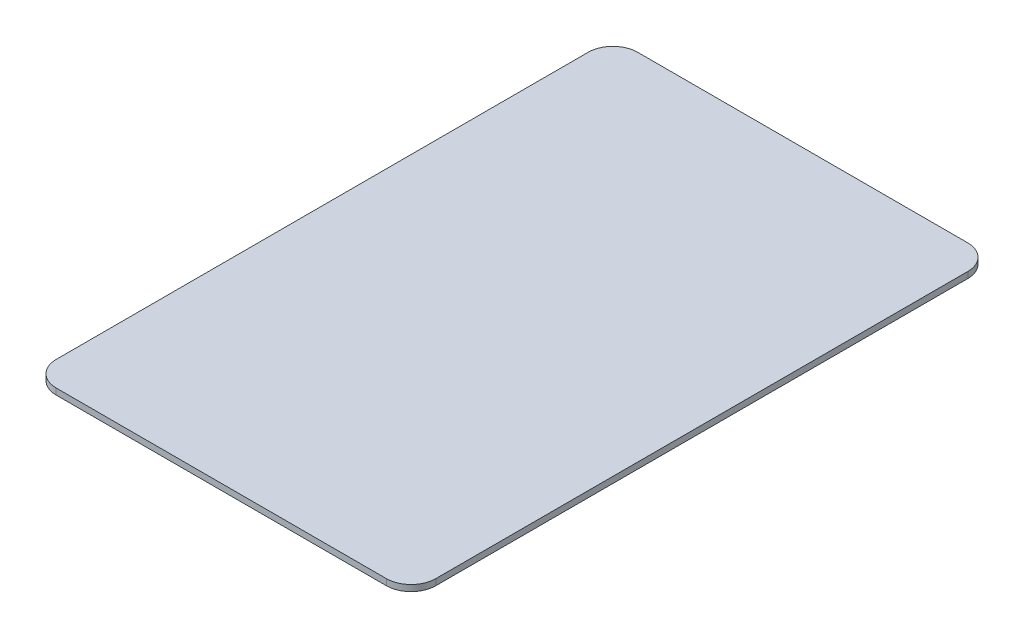
SolidWorks part; units mm, degrees
ref_plane "Front Plane" through (0, 0, 0) normal (0, 0, 1) x (1, 0, 0)
ref_plane "Top Plane" through (0, 0, 0) normal (0, 1, 0) x (1, 0, 0)
ref_plane "Right Plane" through (0, 0, 0) normal (1, 0, 0) x (0, 0, -1)
sketch "Sketch1" plane through (0, 0, 0) normal (0, 1, 0) x (1, 0, 0)
  line L1 (0, 0) -> (97.4242, 0)
  line L2 (0, 0) -> (0, 149.225)
  line L3 (0, 149.225) -> (97.4242, 149.225)
  line L4 (97.4242, 0) -> (97.4242, 149.225)
  dimension "D1" = 97.4242
  dimension "D2" = 149.225
base flange "Base-Flange1" sketch "Sketch1" thickness 1.5875 reverse thickness direction no parameters "D1"=1
fillet "Fillet1" radius 6.35 4 edges at (0, -0.7937, -149.225) (97.4242, -0.7937, -149.225) (0, -0.7937, 0) (97.4242, -0.7937, 0)
sketch "Bend-Lines1" [suppressed] plane through (0, 0, 0) normal (0, 1, 0) x (1, 0, 0)
sketch "Bounding-Box1" [suppressed] plane through (0, 0, 0) normal (0, 1, 0) x (1, 0, 0)
sheet metal parameters "Sheet-Metal1" thickness 1.5875 parameters "D1"=1
flat pattern "Flat-Pattern1" [suppressed]
sketch "Bend-Lines2" plane through (0, 0, 0) normal (0, 1, 0) x (1, 0, 0)
sketch3d "Bounding-Box2" [suppressed]
  line L0 (97.4243, 0, 0) -> (97.4242, 149.225, 0) construction
  line L1 (0, 0, 0) -> (0, 149.225, 0) construction
  line L2 (97.4243, 0, 0) -> (0, 0, 0) construction
  line L3 (97.4242, 149.225, 0) -> (0, 149.225, 0) construction
